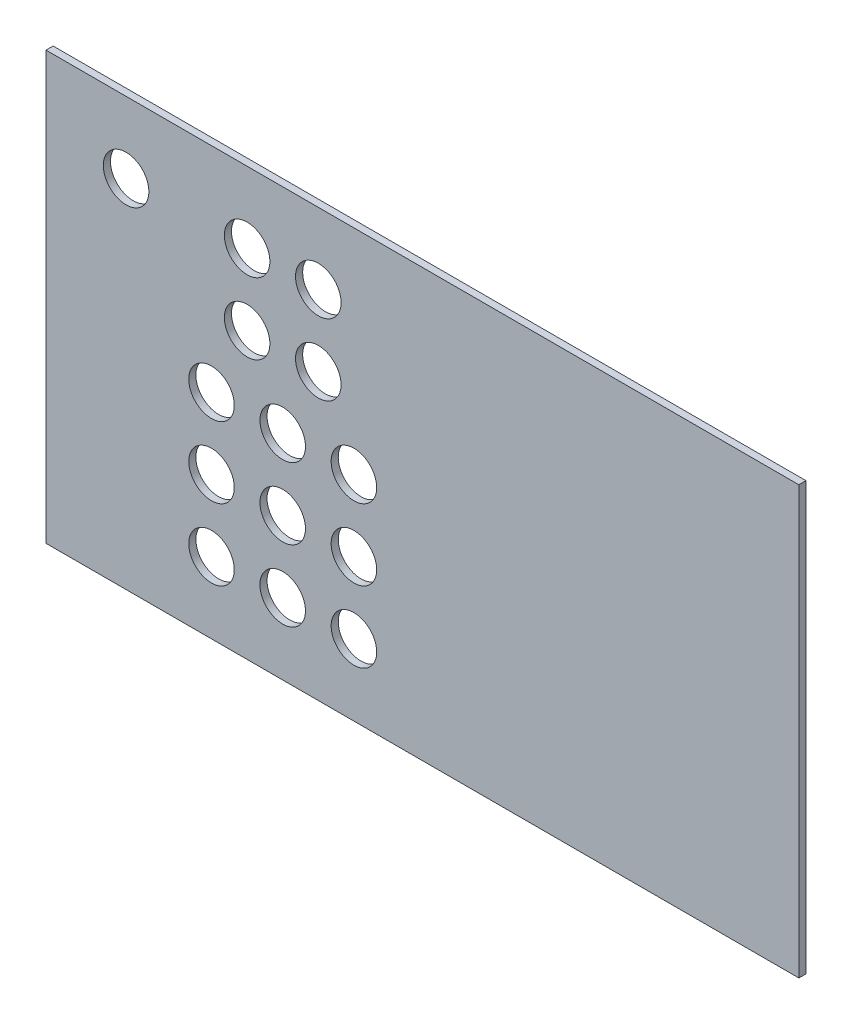
SolidWorks part; units mm, degrees
material "PC High Viscosity"
ref_plane "Front Plane" through (0, 0, 0) normal (0, 0, 1) x (1, 0, 0)
ref_plane "Top Plane" through (0, 0, 0) normal (0, 1, 0) x (1, 0, 0)
ref_plane "Right Plane" through (0, 0, 0) normal (1, 0, 0) x (0, 0, -1)
sketch "Sketch1" plane through (0, 0, 0) normal (0, 0, 1) x (1, 0, 0)
  line L1 (0, 0) -> (381, 0)
  line L2 (0, 0) -> (0, 304.8)
  line L3 (0, 304.8) -> (381, 304.8)
  line L4 (381, 0) -> (381, 304.8)
  dimension "D1" = 381
  dimension "D2" = 304.8
extrude "Boss-Extrude1" add sketch "Sketch1" along normal blind 5.08
sketch "Sketch2" plane through (0, 0, 0) normal (0, 0, -1) x (-1, 0, 0)
  line L1 (-381, 304.8) -> (0, 304.8) construction
  line L2 (-523.4473, 152.4) -> (65.789, 152.4) construction
  dimension "D4" = 152.4
sketch "Sketch3" plane through (0, 0, 0) normal (0, 0, -1) x (-1, 0, 0)
  line L0 (-247.65, 343.5749) -> (-247.65, -43.3065)
  line L1 (-381, 0) -> (-381, 304.8) construction
  line L2 (0, 0) -> (-381, 0) construction
  line L3 (-381, 304.8) -> (0, 304.8) construction
  line L4 (-368.3, 304.8) -> (-501.65, 304.8)
  line L5 (-368.3, 304.8) -> (-368.3, 0)
  line L6 (-368.3, 0) -> (-501.65, 0)
  line L7 (-501.65, 304.8) -> (-501.65, 0)
  line L8 (0, 304.8) -> (0, 0) construction
  line L9 (-2.5625, 304.8) -> (35.5375, 304.8)
  line L10 (-2.5625, 304.8) -> (-2.5625, 0)
  line L11 (-2.5625, 0) -> (35.5375, 0)
  line L12 (35.5375, 304.8) -> (35.5375, 0)
  circle A0 centre (-158.75, 254) radius 16.25
  circle A1 centre (-107.95, 254) radius 16.25
  circle A2 centre (-158.75, 203.2) radius 16.25
  circle A4 centre (-107.95, 203.2) radius 16.25
  circle A5 centre (-133.35, 152.4) radius 16.25
  circle A6 centre (-82.55, 152.4) radius 16.25
  circle A7 centre (-184.15, 152.4) radius 16.25
  circle A8 centre (-133.35, 101.6) radius 16.25
  circle A9 centre (-82.55, 101.6) radius 16.25
  circle A10 centre (-184.15, 101.6) radius 16.25
  circle A11 centre (-133.35, 50.8) radius 16.25
  circle A12 centre (-82.55, 50.8) radius 16.25
  circle A13 centre (-184.15, 50.8) radius 16.25
  circle A14 centre (-21.59, 254) radius 16.256
  dimension "D2" = 32.5
  dimension "D3" = 63.5
  dimension "D4" = 50.8
  dimension "D5" = 50.8
  dimension "D6" = 50.8
  dimension "D7" = 50.8
  dimension "D8" = 50.8
  dimension "D9" = 50.8
  dimension "D10" = 25.4
  dimension "D11" = 50.8
  dimension "D12" = 50.8
  dimension "D13" = 32.512
  dimension "D14" = 86.36
  dimension "D1" = 133.35
  dimension "D15" = 50.8
  dimension "D16" = 254
  dimension "D17" = 12.7
  dimension "D18" = 38.1
  dimension "D19" = 2.5625
  dimension "D20" = 304.8
extrude "Cut-Extrude2" cut sketch "Sketch3" against normal through all contours A0 | A1 | A14 | A2 | A4 | A7 | A5 | A6 | A10 | A8 | A9 | A13 | A11 | A12 region at (158.75, 254, 0) region at (107.95, 254, 0) region at (158.75, 203.2, 0) region at (107.95, 203.2, 0) region at (133.35, 152.4, 0) region at (82.55, 152.4, 0) region at (184.15, 152.4, 0) region at (133.35, 101.6, 0) region at (82.55, 101.6, 0) region at (184.15, 101.6, 0) region at (133.35, 50.8, 0) region at (82.55, 50.8, 0) region at (184.15, 50.8, 0) region at (21.59, 254, 0)
sketch "Sketch4" plane through (0, 0, 0) normal (0, 0, -1) x (-1, 0, 0)
  line L1 (-501.65, 304.8) -> (-368.3, 304.8)
  line L2 (-501.65, 304.8) -> (-501.65, 0)
  line L3 (-501.65, 0) -> (-368.3, 0)
  line L4 (-368.3, 304.8) -> (-368.3, 0)
  line L5 (-2.5625, 304.8) -> (35.5375, 304.8)
  line L6 (-2.5625, 304.8) -> (-2.5625, 0)
  line L7 (-2.5625, 0) -> (35.5375, 0)
  line L8 (35.5375, 304.8) -> (35.5375, 0)
extrude "Boss-Extrude2" add sketch "Sketch4" against normal through all contours L2 L1 L4 L3 | L6 L5 L8 L7
